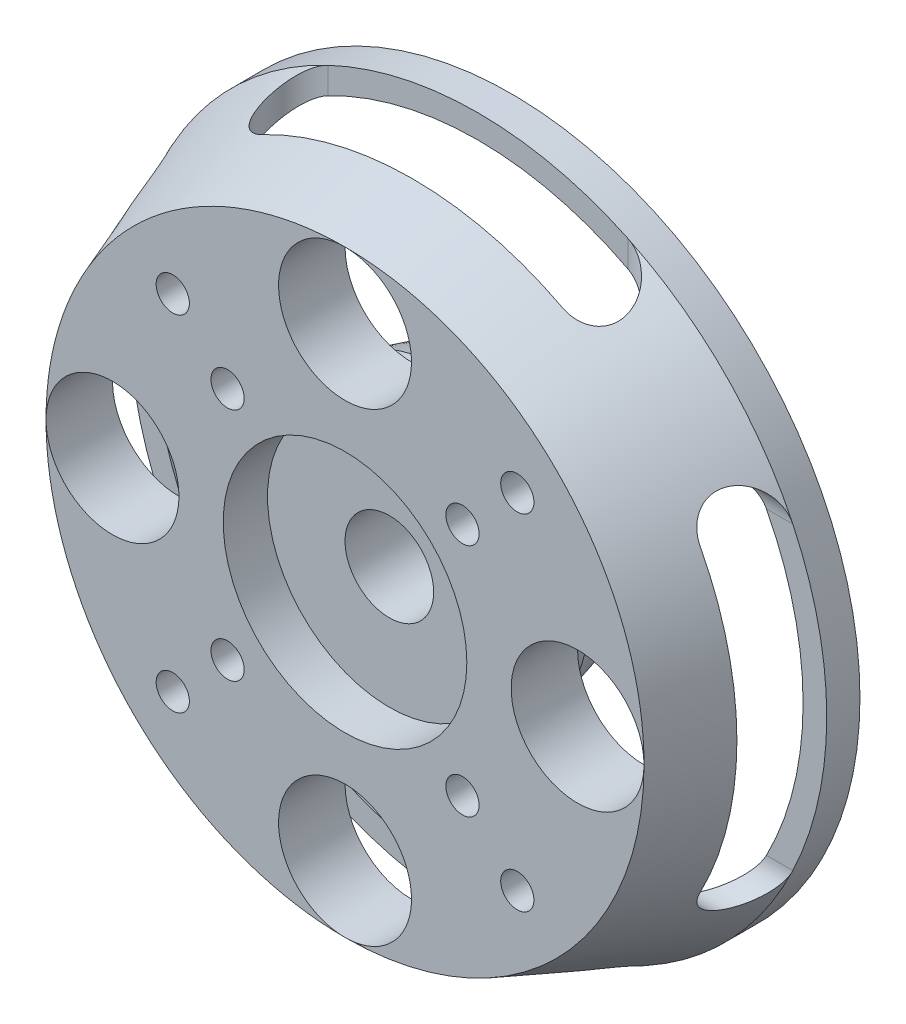
SolidWorks part; units mm, degrees
ref_plane "Front Plane" through (0, 0, 0) normal (0, 0, 1) x (1, 0, 0)
ref_plane "Top Plane" through (0, 0, 0) normal (0, 1, 0) x (1, 0, 0)
ref_plane "Right Plane" through (0, 0, 0) normal (1, 0, 0) x (0, 0, -1)
ref_axis "Z" through (0, 0, -15.75) along (0, 0, 1)
sketch "Sketch1" plane through (0, 0, 0) normal (0, 1, 0) x (1, 0, 0)
  line L0 (29.5, 15) -> (29.5, 12.3627)
  line L1 (29.5, 12.3627) -> (27.114, 6)
  line L2 (27.114, 6) -> (13, 6)
  line L3 (13, 6) -> (13, 9)
  line L4 (11.3923, 15) -> (4, 15)
  line L5 (4, 15) -> (4, 4)
  line L6 (11, 0) -> (27, 0)
  line L7 (27, 0) -> (31.5, 12)
  line L8 (31.5, 12) -> (31.5, 15)
  line L9 (31.5, 15) -> (29.5, 15)
  line L10 (0, -76.8889) -> (0, 67.6055) construction
  line L11 (11, 0) -> (11, 4)
  line L12 (11, 4) -> (4, 4)
  line L13 (4, 4) -> (4, 0) construction
  line L14 (4, 0) -> (11, 0) construction
  line L15 (11.3923, 15) -> (13, 9)
  line L16 (13, 15) -> (11.3923, 15) construction
  line L17 (13, 9) -> (13, 15) construction
  dimension "D1" = 8
  dimension "D2" = 15
  dimension "D3" = 2
  dimension "D4" = 3
  dimension "D5" = 2
  dimension "D6" = 63
  dimension "D7" = 6
  dimension "D8" = 9
  dimension "D9" = 54
  dimension "D10" = 22
  dimension "D11" = 4
  dimension "D12" = 15
  dimension "D13" = 3
revolve "Revolve1" add sketch "Sketch1" angle 360 about L10
ref_plane "Plane4" through (-31.5, 0, 0) normal (-1, 0, 0) x (0, 0, 1)
sketch "Sketch2" plane through (-31.5, 0, 0) normal (-1, 0, 0) x (0, 0, 1)
  line L0 (-9.05, -13.55) -> (-9.05, 13.55) construction
  line L1 (-12, -13.55) -> (-12, 13.55)
  line L2 (-6.1, -13.55) -> (-6.1, 13.55)
  line L3 (-15.75, 0) -> (0.75, 0) construction
  line L4 (-12.4387, -16.5) -> (-5.6613, -16.5) construction
  line L5 (-12.4387, 16.5) -> (-5.6613, 16.5) construction
  line L7 (-15, 29.5) -> (-15, -29.5) construction
  arc A0 (-12, -13.55) -> (-6.1, -13.55) centre (-9.05, -13.55) ccw
  arc A1 (-6.1, 13.55) -> (-12, 13.55) centre (-9.05, 13.55) ccw
  point P2 (-9.05, 0)
  dimension "D2" = 33
  dimension "D1" = 5.9
  dimension "D3" = 3
extrude "Cut-Extrude1" cut sketch "Sketch2" against normal blind 10
pattern_circular "CirPattern1" count 4 over 360 about axis through (0, 0, -15.75) along (0, 0, 1) of "Cut-Extrude1"
sketch "Sketch3" plane through (0, 0, 0) normal (0, 0, 1) x (1, 0, 0)
  line L0 (-21, 0) -> (0, 0) construction
  line L1 (0, 0) -> (-15.5563, 15.5563) construction
  circle A0 centre (-21, 0) radius 6
  circle A1 centre (0, 21) radius 6
  circle A2 centre (21, 0) radius 6
  circle A3 centre (0, -21) radius 6
  circle A4 centre (-15.5563, 15.5563) radius 1.5
  circle A5 centre (-10.6066, 10.6066) radius 1.5
  circle A6 centre (10.6066, 10.6066) radius 1.5
  circle A7 centre (15.5563, 15.5563) radius 1.5
  circle A8 centre (10.6066, -10.6066) radius 1.5
  circle A9 centre (15.5563, -15.5563) radius 1.5
  circle A10 centre (-10.6066, -10.6066) radius 1.5
  circle A11 centre (-15.5563, -15.5563) radius 1.5
  point P13 (0, 0)
  point P31 (0, 0)
  dimension "D1" = 12
  dimension "D5" = 3
  dimension "D2" = 21
  dimension "D4" = 45
  dimension "D6" = 7
  dimension "D7" = 15
  dimension "D3" = 4
  dimension "D8" = 4
extrude "Cut-Extrude2" cut sketch "Sketch3" against normal through all
equation "\"RotorMainLength\"= 41'rotor body longest dimension"
equation "\"OverallLength\"= 65.8'The height of the whole motor, not counting shaft protrusions"
equation "\"RotorDiameter\"= 63'Overall rotor diameter"
equation "\"RotorTopCapHeight\"= 14'Rough measurement/eyeballed. Not super critical for this; most important dim is overall length"
equation "\"RotorLargeHoleDiameter\"= 17'ID measurement with calipers"
equation "\"RotorLargeHoleTangentSpacing\"= 19'tangent to tangent on the large holes. add one diameter to achieve the center distances"
equation "\"RotorLargeHoleCenterDistance\"= \"RotorLargeHoleTangentSpacing\" + \"RotorLargeHoleDiameter\"'Center to center spacing for large hole"
equation "\"RotorSmallHoleID\"= 8'ID measurement with calipers"
equation "\"RotorSmallHoleTangentSpacing\"= 37'Tangent to Tangent (rounded to the nearest integer, real measurement was like 0.03mm off)"
equation "\"RotorSmallHoleCenterDistance\"= \"RotorSmallHoleID\" + \"RotorSmallHoleTangentSpacing\"'Center to center spacing for small holes"
equation "\"ShaftDiameter\"= 8"
equation "\"RotorShaftTopCapDiameter\"= 18'the small circular extrusion at the top of the rotor"
equation "\"RotorShaftTopCapHeight\"= 2'Height of the small cylindircal extrusion at the top of the rotor"
equation "\"RotorBoltCircleFlatDiameter\"= 30'Diameter of the flat portion where the bolt circle is drilled in the rotor"
equation "\"RotorTaperedEdgeHeight\"= 7'approximate, vertical distance of the tapered/angled edge of the rotor"
equation "\"RotorBoltCircleCenterDistance\"= 23mm'rounded, hard to measure with calipers so assuming they aren't fucking insane and chose this"
equation "\"StatorTrayHeight\"= 3+6+6\t'Rough measurement/eyeballed. Not super critical. Take up clearance in airgap; maintain overall height"
equation "\"StatorBaseOD\" = 54.00\t\t'OD of the base of the stator where the bolt circle is"
equation "\"StatorBoltCircleInnerRadius\"= 15"
equation "\"StatorBoltCircleDistance\"= 7"
equation "\"D1@Sketch1\"=\"ShaftDiameter\""
equation "\"D2@Sketch1\"=\"StatorTrayHeight\""
equation "\"D6@Sketch1\"=\"RotorDiameter\""
equation "\"D7@Sketch3\" = \"StatorBoltCircleInnerRadius\""
equation "\"D6@Sketch3\" = \"StatorBoltCircleDistance\""
equation "\"D1@Sketch3\"=12"
equation "\"D9@Sketch1\" = \"StatorBaseOD\""
